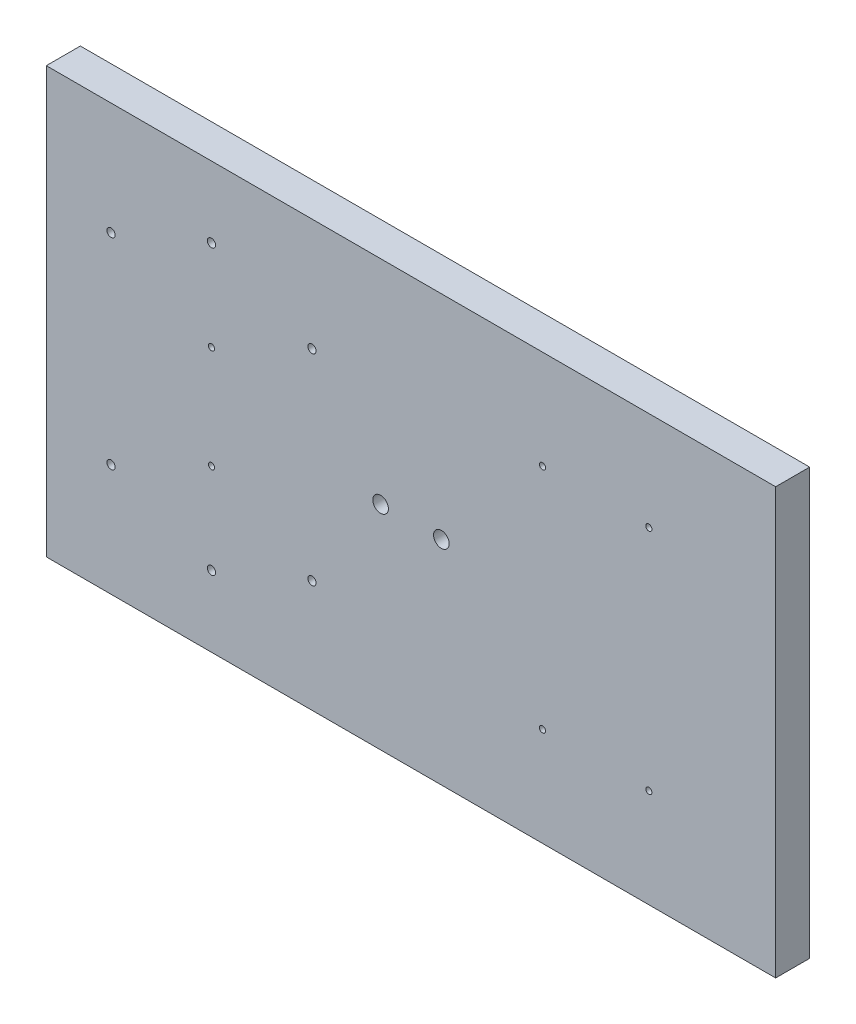
SolidWorks part; units mm, degrees
material "1060 Alloy"
ref_plane "Front Plane" through (0, 0, 0) normal (0, 0, 1) x (1, 0, 0)
ref_plane "Top Plane" through (0, 0, 0) normal (0, 1, 0) x (1, 0, 0)
ref_plane "Right Plane" through (0, 0, 0) normal (1, 0, 0) x (0, 0, -1)
sketch "Sketch1" plane through (0, 0, 0) normal (0, 0, 1) x (1, 0, 0)
  line L1 (-152.4, -88.9) -> (152.4, -88.9)
  line L2 (-152.4, -88.9) -> (-152.4, 88.9)
  line L3 (-152.4, 88.9) -> (152.4, 88.9)
  line L4 (152.4, -88.9) -> (152.4, 88.9)
  line L5 (-152.4, -88.9) -> (152.4, 88.9) construction
  line L6 (-152.4, 88.9) -> (152.4, -88.9) construction
  point P0 (0, 0)
  dimension "D1" = 304.8
  dimension "D2" = 177.8
extrude "Boss-Extrude1" add sketch "Sketch1" along normal blind 14.224
hole_wizard "Tap Drill for #8-32 Tap1" positions "Sketch3" profile "Sketch5" hole size "#8-32" standard "ANSI Inch"
sketch "Sketch3" plane through (0, 0, 14.224) normal (0, 0, 1) x (1, 0, 0)
  point P0 (-41.39, 41.985)
  point P3 (-41.39, -41.985)
  point P6 (-125.36, -41.985)
  point P9 (-125.36, 41.985)
  point P30 (-83.375, 59.2455)
  point P33 (-83.375, -59.2455)
sketch "Sketch5" plane through (-41.39, 41.985, 14.224) normal (1, 0, 0) x (0, -1, 0)
  line L0 (0, 0) -> (0, 8.9118)
  line L1 (0, 8.9118) -> (1.7272, 7.874)
  line L2 (1.7272, 7.874) -> (1.7272, 0)
  line L5 (1.7272, 0) -> (0, 0)
  line L10 (0, 8.9118) -> (-1.7272, 7.874) construction
  line L11 (0, -6.35) -> (0, 107.95) construction
  dimension "Hole Dia." = 3.4544
  dimension "Hole Depth" = 7.874
  dimension "Drill Angle" = 118
hole_wizard "Tap Drill for #5-40 Tap1" positions "Sketch6" profile "Sketch7" hole size "#5-40" standard "ANSI Inch"
sketch "Sketch6" plane through (0, 0, 14.224) normal (0, 0, 1) x (1, 0, 0)
  point P0 (-83.375, 21.5)
  point P3 (-83.375, -21.5)
  point P13 (54.9507, 47.625)
  point P15 (99.4007, 47.625)
  point P17 (99.4007, -47.625)
  point P19 (54.9507, -47.625)
sketch "Sketch7" plane through (-83.375, 21.5, 14.224) normal (1, 0, 0) x (0, -1, 0)
  line L0 (0, 0) -> (0, 8.6485)
  line L1 (0, 8.6485) -> (1.289, 7.874)
  line L2 (1.289, 7.874) -> (1.289, 0)
  line L5 (1.289, 0) -> (0, 0)
  line L10 (0, 8.6485) -> (-1.2891, 7.874) construction
  line L11 (0, -6.35) -> (0, 107.95) construction
  dimension "Hole Dia." = 2.5781
  dimension "Hole Depth" = 7.874
  dimension "Drill Angle" = 118
sketch "Sketch8" plane through (0, 0, 14.224) normal (0, 0, 1) x (1, 0, 0)
  line L0 (-83.375, 21.5) -> (-83.375, -21.5) construction
  line L1 (-104.875, 0) -> (-61.875, 0) construction
  line L2 (78.1803, 50.8) -> (78.1803, -50.8) construction
  line L3 (52.7803, 50.8) -> (103.5803, 50.8) construction
  line L4 (103.5803, -50.8) -> (52.7803, -50.8) construction
  line L5 (65.173, 0) -> (91.1876, 0) construction
  point P8 (-83.375, 0)
  point P18 (78.1803, 0)
hole_wizard "1/4 Clearance Hole1" positions "Sketch9" profile "Sketch10" hole size "1/4" standard "ANSI Inch" end condition through all
sketch "Sketch9" plane through (0, 0, 0) normal (0, 0, 1) x (1, 0, 0)
  line L0 (-152.4, 88.9) -> (152.4, -88.9) construction
  line L2 (0, 0) -> (12.7, 0) construction
  line L4 (0, 0) -> (-12.7, 0) construction
  point P8 (12.7, 0)
  point P13 (-12.7, 0)
  dimension "D1" = 12.7
sketch "Sketch10" plane through (-12.7, 0, 0) normal (1, 0, 0) x (0, 1, 0)
  line L0 (0, 0) -> (0, 14.224)
  line L1 (0, 14.224) -> (3.2639, 14.224)
  line L2 (3.2639, 14.224) -> (3.2639, 0)
  line L5 (3.2639, 0) -> (0, 0)
  line L11 (0, -6.35) -> (0, 107.95) construction
  dimension "Thru Hole Dia." = 6.5278
  dimension "Thru Hole Depth" = 14.224
